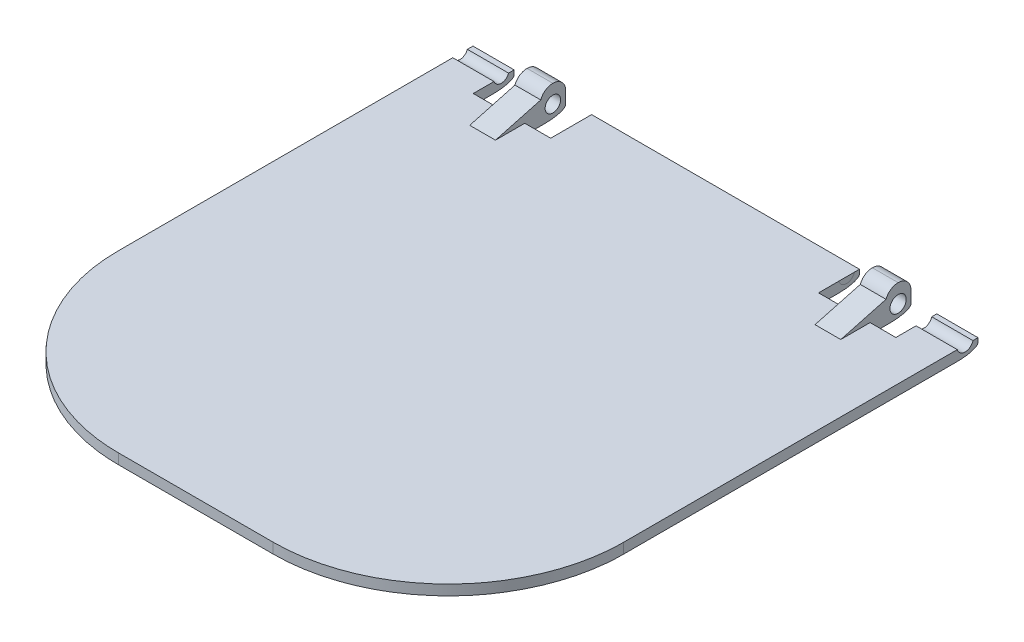
SolidWorks part; units mm, degrees
ref_plane "Płaszczyzna przednia" through (0, 0, 0) normal (0, 0, 1) x (1, 0, 0)
ref_plane "Płaszczyzna górna" through (0, 0, 0) normal (0, 1, 0) x (1, 0, 0)
ref_plane "Płaszczyzna prawa" through (0, 0, 0) normal (1, 0, 0) x (0, 0, -1)
sketch "Sketch1" plane through (0, 0, 0) normal (0, 1, 0) x (1, 0, 0)
  line L0 (-124.9901, 1941.929) -> (-26.9901, 1941.929)
  line L1 (-26.9901, 1941.929) -> (-26.9901, 1869.1775)
  line L2 (-124.9901, 1941.929) -> (-124.9901, 1869.1775)
  line L4 (-91.0115, 1835.1775) -> (-61.0115, 1835.1775)
  spline S0 degree 3 poles (-124.9901, 1869.1775) (-125.0317, 1863.8824) (-123.3191, 1856.8126) (-118.1757, 1848.3345) (-113.1696, 1842.9476) (-104.1277, 1837.0374) (-96.2354, 1835.1656) (-91.0115, 1835.1775) knots 0 0 0 0 0.297125 0.397303 0.556358 0.706503 1 1 1 1
  spline S1 degree 3 poles (-26.9901, 1869.1775) (-26.9715, 1862.1042) (-30.0087, 1852.8896) (-37.9374, 1843.8406) (-46.6433, 1837.4274) (-55.2239, 1835.1602) (-61.0115, 1835.1775) knots 0 0 0 0 0.396907 0.51803 0.674279 1 1 1 1
extrude "Boss-Extrude1" add sketch "Sketch1" along normal blind 2
sketch "Sketch5" plane through (-26.9901, 0, 0) normal (1, 0, 0) x (0, 0, -1)
  line L0 (1869.1775, 2) -> (1941.929, 2) construction
  line L1 (1937.929, 2) -> (1941.929, 2)
  line L2 (1937.929, 2) -> (1937.929, 0)
  line L3 (1937.929, 0) -> (1941.929, 0)
  line L4 (1941.929, 2) -> (1941.929, 0)
  line L5 (1937.929, 2.5) -> (1937.929, 0) construction
extrude "Cut-Extrude3" cut sketch "Sketch5" against normal blind 123
fillet "Fillet3" radius 1.2 1 edges at (-75.9901, 0, -1937.929) second distance 4 first distance on face at (-75.9901, 1, -1937.929)
sketch "Sketch6" plane through (0, 2, 0) normal (0, 1, 0) x (1, 0, 0)
  line L0 (-124.9901, 1937.929) -> (-26.9901, 1937.929) construction
  line L1 (-44.9901, 1937.929) -> (-39.9901, 1937.929)
  line L2 (-44.9901, 1937.929) -> (-44.9901, 1932.929)
  line L3 (-44.9901, 1932.929) -> (-39.9901, 1932.929)
  line L4 (-39.9901, 1937.929) -> (-39.9901, 1932.929)
  line L5 (-44.9901, 1935.429) -> (-44.9901, 1937.929) construction
  line L6 (-106.9901, 1937.929) -> (-106.9901, 1935.429) construction
  line L7 (-111.9901, 1932.929) -> (-106.9901, 1932.929)
  line L8 (-111.9901, 1932.929) -> (-111.9901, 1937.929)
  line L9 (-111.9901, 1937.929) -> (-106.9901, 1937.929)
  line L10 (-106.9901, 1932.929) -> (-106.9901, 1937.929)
extrude "Boss-Extrude3" add sketch "Sketch6" along normal blind 4
fillet "Fillet4" radius 2.5 4 edges at (-42.4901, 6, -1932.929) (-42.4901, 6, -1937.929) (-109.4901, 6, -1932.929) (-109.4901, 6, -1937.929)
sketch "Sketch7" plane through (-111.9901, 0, 0) normal (-1, 0, 0) x (0, 0, 1)
  circle A0 centre (-1935.429, 2.5) radius 1.5
extrude "Cut-Extrude7" cut sketch "Sketch7" against normal blind 10 and the other way blind 23
sketch "Sketch8" plane through (-39.9901, 0, 0) normal (1, 0, 0) x (0, 0, -1)
  circle A0 centre (1935.429, 2.4211) radius 1.5789
extrude "Cut-Extrude8" cut sketch "Sketch8" against normal blind 10 and the other way blind 103
sketch "Sketch11" plane through (0, 2, 0) normal (0, 1, 0) x (1, 0, 0)
  line L1 (-111.9901, 1937.929) -> (-116.9901, 1937.929)
  line L2 (-111.9901, 1937.929) -> (-111.9901, 1929.9876)
  line L3 (-111.9901, 1929.9876) -> (-116.9901, 1929.9876)
  line L4 (-116.9901, 1937.929) -> (-116.9901, 1929.9876)
  line L5 (-106.9901, 1937.929) -> (-101.9646, 1937.929)
  line L6 (-106.9901, 1937.929) -> (-106.9901, 1929.9876)
  line L7 (-106.9901, 1929.9876) -> (-101.9646, 1929.9876)
  line L8 (-101.9646, 1937.929) -> (-101.9646, 1929.9876)
  line L9 (-44.9901, 1937.929) -> (-49.9868, 1937.929)
  line L10 (-44.9901, 1937.929) -> (-44.9901, 1929.9876)
  line L11 (-44.9901, 1929.9876) -> (-49.9868, 1929.9876)
  line L12 (-49.9868, 1937.929) -> (-49.9868, 1929.9876)
  line L13 (-39.9901, 1937.929) -> (-34.9897, 1937.929)
  line L14 (-39.9901, 1937.929) -> (-39.9901, 1929.9876)
  line L15 (-39.9901, 1929.9876) -> (-34.9897, 1929.9876)
  line L16 (-34.9897, 1937.929) -> (-34.9897, 1929.9876)
extrude "Cut-Extrude10" cut sketch "Sketch11" against normal blind 2
sketch "Sketch12" plane through (-111.9901, 0, 0) normal (-1, 0, 0) x (0, 0, 1)
  line L0 (-1924.2999, 2) -> (-1934.1704, 4.6601)
  line L1 (-1934.0148, 2) -> (-1869.1775, 2) construction
  line L2 (-1933.0203, 1.89) -> (-1924.2999, 2)
  spline S0 degree 3 poles (-1934.1704, 4.6601) (-1933.9417, 4.3436) (-1933.42, 3.9827) (-1933.0445, 2.9851) (-1932.9215, 2.3465) (-1933.0203, 1.89) knots 0 0 0 0 0.374528 0.573862 1 1 1 1
extrude "Boss-Extrude9" add sketch "Sketch12" against normal blind 5
sketch "Sketch13" plane through (-39.9901, 0, 0) normal (1, 0, 0) x (0, 0, -1)
  line L0 (1933.0843, 4.3674) -> (1924.2999, 2)
  line L1 (1924.2999, 2) -> (1933.0579, 2)
  line L2 (1869.1775, 2) -> (1933.9074, 2) construction
  line L3 (1933.0579, 2) -> (1933.342, 3.33)
  line L4 (1933.342, 3.33) -> (1934.068, 4.2678)
  line L5 (1934.068, 4.2678) -> (1934.6124, 4.7319)
  line L6 (1934.6124, 4.7319) -> (1933.0843, 4.3674)
extrude "Boss-Extrude10" add sketch "Sketch13" against normal blind 5
